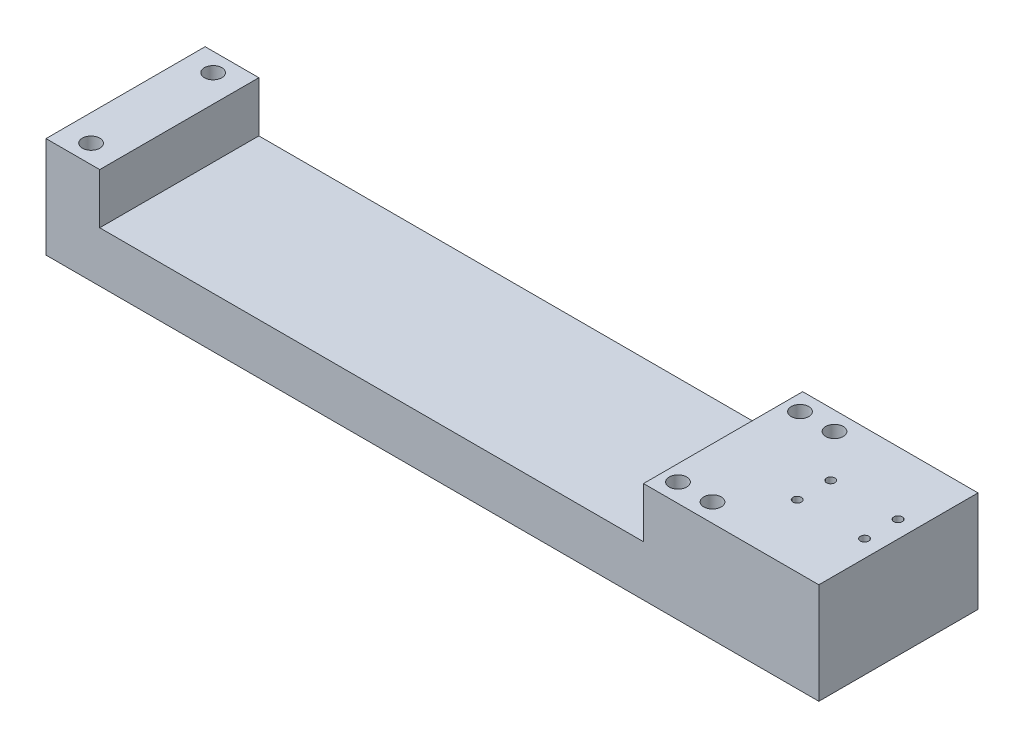
SolidWorks part; units mm, degrees
material "6061 Alloy"
ref_plane "Front Plane" through (0, 0, 0) normal (0, 0, 1) x (1, 0, 0)
ref_plane "Top Plane" through (0, 0, 0) normal (0, 1, 0) x (1, 0, 0)
ref_plane "Right Plane" through (0, 0, 0) normal (1, 0, 0) x (0, 0, -1)
sketch "Sketch1" plane through (0, 0, 0) normal (0, 0, 1) x (1, 0, 0)
  line B0 (-125.125, 38.05) -> (-104.875, 38.05)
  line B1 (-104.875, 38.05) -> (-104.875, 19.05)
  line B2 (-104.875, 19.05) -> (100.125, 19.05)
  line B3 (100.125, 19.05) -> (100.125, 38.05)
  line B4 (100.125, 38.05) -> (125.125, 38.05)
  line B5 (-125.125, 38.05) -> (-125.125, 0)
  line B6 (-125.125, 0) -> (125.125, 0)
  line B7 (125.125, 38.05) -> (166.225, 38.05)
  line B8 (166.225, 38.05) -> (166.225, 0)
  line B9 (166.225, 0) -> (125.125, 0)
sketch_block_instance "Block-MainBlock Sideview-1"
sketch_block "Block-MainBlock Sideview" parameters "D1"=19.05, "D2"=38.05
extrude "Boss-Extrude1" add sketch "Sketch1" along normal blind 60
sketch "Sketch3" plane through (0, 38.05, 0) normal (0, 1, 0) x (1, 0, 0)
  line B0 (-105.125, 0) -> (-105.125, -60)
  line B1 (-105.125, 0) -> (-125.125, 0)
  line B2 (-125.125, 0) -> (-125.125, -60)
  line B3 (-105.125, -60) -> (-125.125, -60)
  line B4 (125.125, 0) -> (125.125, -60)
  line B5 (125.125, 0) -> (100.125, 0)
  line B6 (100.125, 0) -> (100.125, -60)
  line B7 (125.125, -60) -> (100.125, -60)
  circle B8 centre (-115.125, -53) radius 3.3
  circle B9 centre (119.125, -7) radius 3.3
  circle B10 centre (106.125, -7) radius 3.3
  circle B11 centre (119.125, -53) radius 3.3
  circle B12 centre (106.125, -53) radius 3.3
  circle B13 centre (-115.125, -7) radius 3.3
sketch_block_instance "Block-MainBlock Topview-1"
sketch_block "Block-MainBlock Topview"
extrude "Cut-Extrude1" cut sketch "Sketch3" against normal blind 6.35 contours B12 | B11 | B10 | B9 | B8 | B13 region at (-115.125, 38.05, 53) region at (119.125, 38.05, 7) region at (106.125, 38.05, 7) region at (119.125, 38.05, 53) region at (106.125, 38.05, 53) region at (-115.125, 38.05, 7)
sketch "Sketch4" plane through (0, 38.05, 0) normal (0, 1, 0) x (1, 0, 0)
  line B0 (128.025, -20.5) -> (166.125, -20.5) construction
  line B1 (166.225, 0) -> (100.125, 0)
  line B2 (100.125, 0) -> (100.125, -60)
  line B3 (100.125, -60) -> (166.225, -60)
  line B4 (166.225, -60) -> (166.225, 0)
  line B5 (128.025, -20.5) -> (128.025, -39.5) construction
  line B6 (128.025, -39.5) -> (166.125, -39.5) construction
  circle B7 centre (159.775, -23.675) radius 1.5875
  circle B8 centre (134.375, -36.325) radius 1.5875
  circle B9 centre (159.775, -36.325) radius 1.5875
  circle B10 centre (134.375, -23.675) radius 1.5875
sketch_block_instance "Block-MotorMounting TopView-1"
sketch_block "Block-MotorMounting TopView"
extrude "Cut-Extrude2" cut sketch "Sketch4" against normal blind 6.35 contours B10 | B7 | B9 | B8 region at (159.775, 38.05, 23.675) region at (134.375, 38.05, 36.325) region at (159.775, 38.05, 36.325) region at (134.375, 38.05, 23.675)
